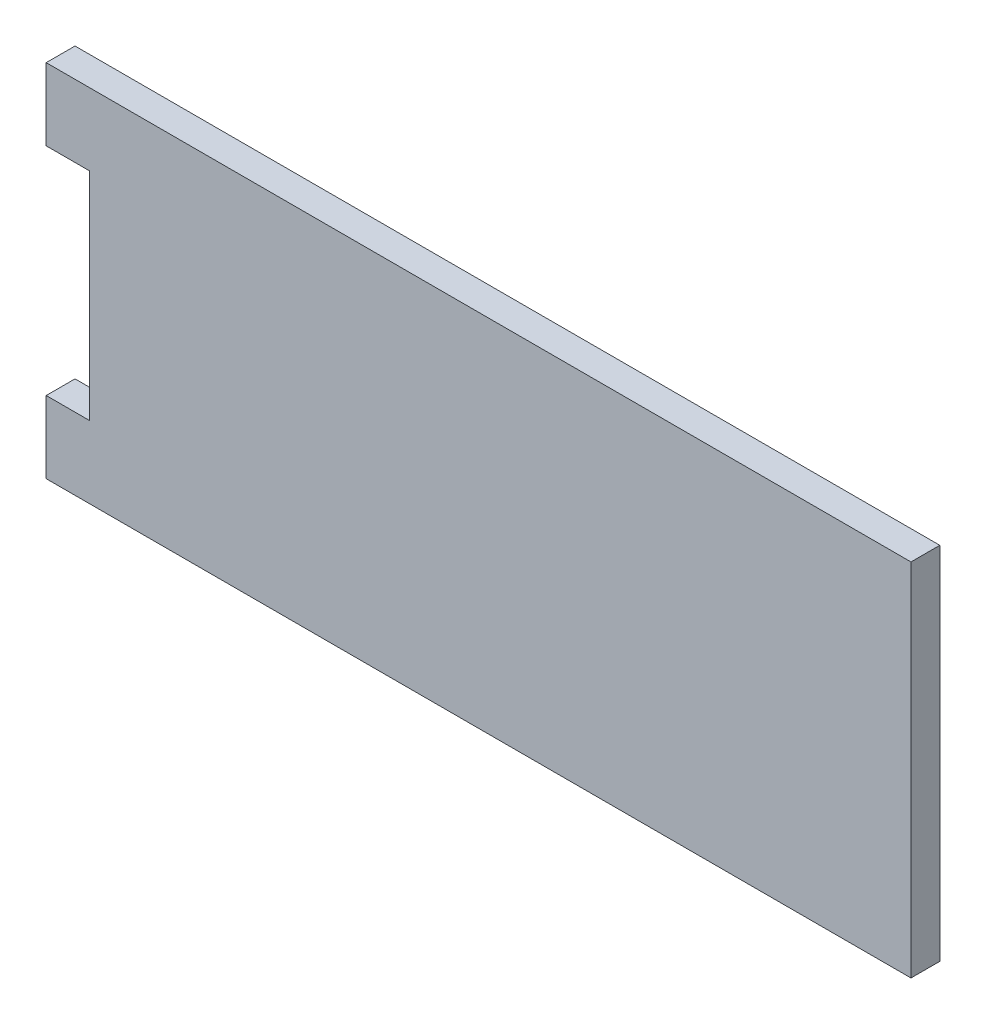
SolidWorks part; units mm, degrees
ref_plane "Front Plane" through (0, 0, 0) normal (0, 0, 1) x (1, 0, 0)
ref_plane "Top Plane" through (0, 0, 0) normal (0, 1, 0) x (1, 0, 0)
ref_plane "Right Plane" through (0, 0, 0) normal (1, 0, 0) x (0, 0, -1)
sketch "Sketch1" plane through (0, 0, 0) normal (0, 0, 1) x (1, 0, 0)
  line L1 (-60, 25) -> (60, 25)
  line L2 (-60, 25) -> (-60, -25)
  line L3 (-60, -25) -> (60, -25)
  line L4 (60, 25) -> (60, -25)
  point P4 (0, 25)
  point P6 (60, 0)
  dimension "D1" = 50
  dimension "D2" = 120
extrude "Boss-Extrude1" add sketch "Sketch1" along normal blind 4
sketch "Sketch2" plane through (0, 0, 4) normal (0, 0, 1) x (1, 0, 0)
  line L0 (-60, 25) -> (-60, -25) construction
  line L1 (-68.5772, 15) -> (-54, 15)
  line L2 (-68.5772, 15) -> (-68.5772, -15)
  line L3 (-68.5772, -15) -> (-54, -15)
  line L4 (-54, 15) -> (-54, -15)
  point P4 (-54, 0)
  point P7 (-60, 0)
  dimension "D1" = 30
  dimension "D2" = 6
extrude "Cut-Extrude1" cut sketch "Sketch2" against normal up to next
